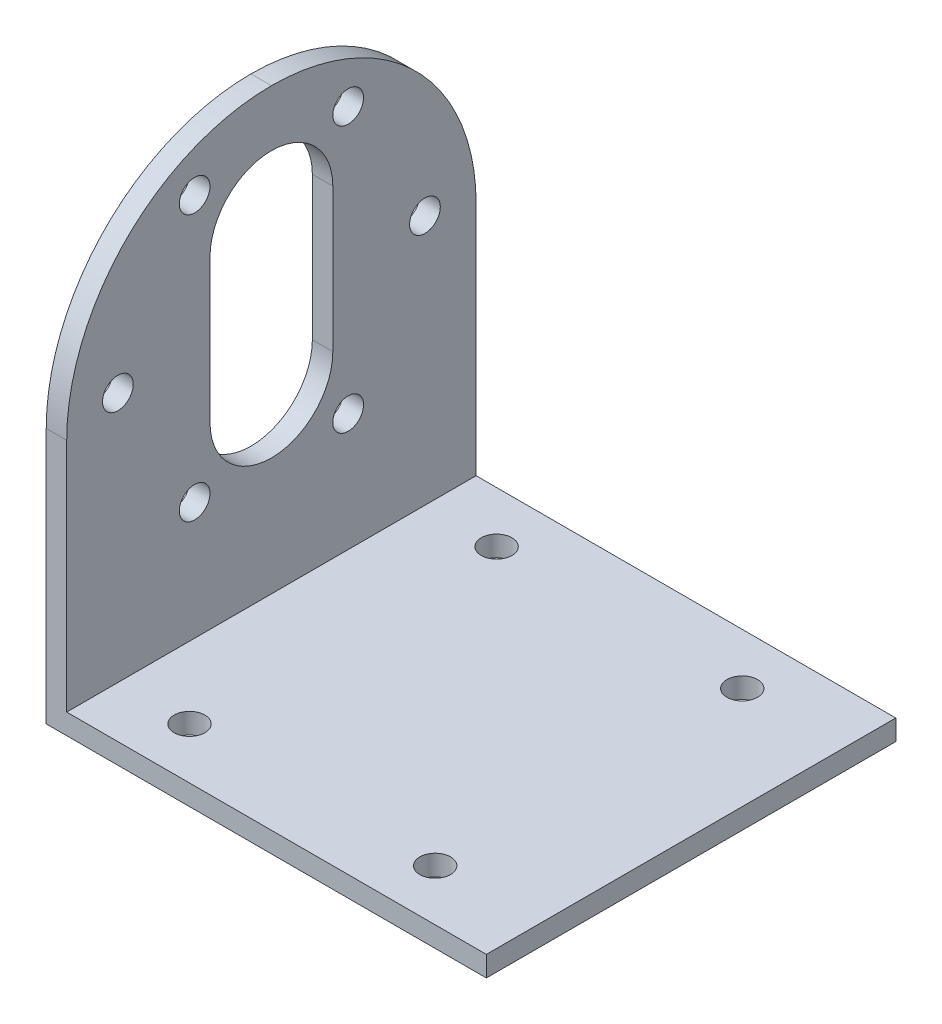
SolidWorks part; units mm, degrees
material "灰铸铁"
ref_plane "前视基准面" through (0, 0, 0) normal (0, 0, 1) x (1, 0, 0)
ref_plane "上视基准面" through (0, 0, 0) normal (0, 1, 0) x (1, 0, 0)
ref_plane "右视基准面" through (0, 0, 0) normal (1, 0, 0) x (0, 0, -1)
sketch "草图1" plane through (0, 0, 0) normal (0, 0, 1) x (1, 0, 0)
  line L0 (0, 0) -> (0, 43)
  line L1 (0, 0) -> (41, 0)
  dimension "D1" = 43
  dimension "D2" = 41
extrude "拉伸-薄壁1" add sketch "草图1" along normal blind 40 thin thin type one direction wall 2
sketch "草图2" plane through (-2, 0, 0) normal (-1, 0, 0) x (0, 0, 1)
  line L0 (-981.6198, 24.5) -> (49018.3802, 24.5) construction
  line L1 (20, -1002) -> (20, 48998) construction
  line L2 (40, -2) -> (0, -2) construction
  circle A0 centre (35, 24.5) radius 1.5
  circle A1 centre (27.5, 11.5096) radius 1.5
  circle A2 centre (12.5, 11.5096) radius 1.5
  circle A3 centre (5, 24.5) radius 1.5
  circle A4 centre (12.5, 37.4904) radius 1.5
  circle A5 centre (27.5, 37.4904) radius 1.5
  point P9 (20, -2)
  point P21 (20, 24.5)
  dimension "D1" = 3
  dimension "D3" = 15
  dimension "D2" = 26.5
  dimension "D4" = 6
extrude "切除-拉伸1" cut sketch "草图2" against normal through all
fillet "圆角1" radius 20 2 edges at (-1, 43, 40) (-1, 43, 0)
sketch "草图3" plane through (-2, 0, 0) normal (-1, 0, 0) x (0, 0, 1)
  line L0 (20, 31.5) -> (20, 17.5) construction
  line L1 (26, 31.5) -> (26, 17.5)
  line L2 (14, 31.5) -> (14, 17.5)
  line L3 (40, -2) -> (0, -2) construction
  line L4 (5, 24.5) -> (20, 24.5) construction
  arc A0 (26, 31.5) -> (14, 31.5) centre (20, 31.5) ccw
  arc A1 (14, 17.5) -> (26, 17.5) centre (20, 17.5) ccw
  point P2 (20, 24.5)
  point P9 (20, -2)
  dimension "D1" = 6
  dimension "D2" = 7
extrude "切除-拉伸2" cut sketch "草图3" against normal through all
sketch "草图4" plane through (0, 0, 0) normal (0, 1, 0) x (1, 0, 0)
  line L0 (7, -35) -> (31, -35) construction
  line L1 (7, -5) -> (31, -5) construction
  line L2 (31, -5) -> (31, -35) construction
  line L3 (31, -20) -> (41, -20) construction
  line L4 (41, -40) -> (41, 0) construction
  circle A0 centre (7, -35) radius 1.5
  circle A1 centre (31, -35) radius 1.5
  circle A2 centre (31, -5) radius 1.5
  circle A3 centre (7, -5) radius 1.5
  dimension "D1" = 3
  dimension "D4" = 30
  dimension "D5" = 24
  dimension "D6" = 10
  dimension "D2" = 2
  dimension "D3" = 2
extrude "切除-拉伸3" cut sketch "草图4" against normal through all
